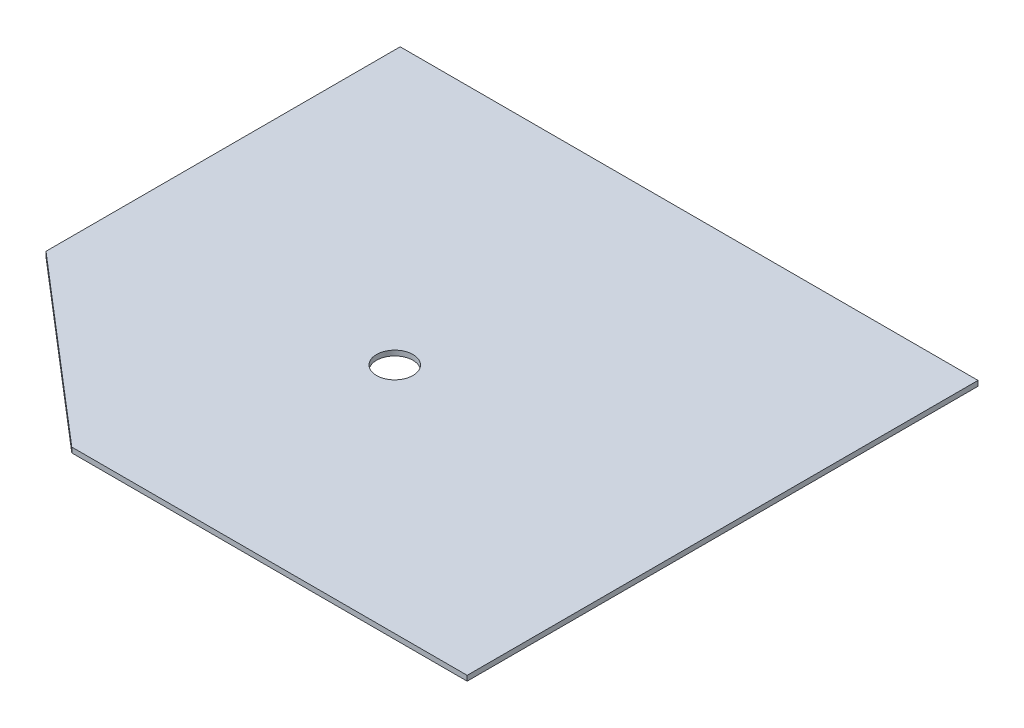
SolidWorks part; units mm, degrees
ref_plane "Front Plane" through (0, 0, 0) normal (0, 0, 1) x (1, 0, 0)
ref_plane "Top Plane" through (0, 0, 0) normal (0, 1, 0) x (1, 0, 0)
ref_plane "Right Plane" through (0, 0, 0) normal (1, 0, 0) x (0, 0, -1)
sketch "Sketch1" plane through (0, 0, 0) normal (0, 1, 0) x (1, 0, 0)
  line L1 (-213.645, -182.0895) -> (238.815, -182.0895)
  line L2 (-213.645, -182.0895) -> (-213.645, 217.9105)
  line L3 (-213.645, 217.9105) -> (238.815, 217.9105)
  line L4 (238.815, -182.0895) -> (238.815, 217.9105)
  dimension "D1" = 452.46
  dimension "D2" = 213.645
  dimension "D3" = 400
extrude "Boss-Extrude1" add sketch "Sketch1" along normal blind 4
sketch "Sketch2" plane through (0, 4, 0) normal (0, -1, 0) x (1, 0, 0)
  circle A0 centre (0, 0) radius 14.275
  dimension "D1" = 28.55
extrude "Cut-Extrude1" cut sketch "Sketch2" along normal through all
sketch "Sketch3" plane through (0, 4, 0) normal (0, 1, 0) x (1, 0, 0)
  line L0 (-70.7913, -182.0895) -> (-213.645, -59.422)
  line L1 (-213.645, -182.0895) -> (238.815, -182.0895) construction
  line L2 (-213.645, 217.9105) -> (-213.645, -182.0895) construction
  line L3 (-213.645, -59.422) -> (-317.3581, -168.1086)
  line L4 (-317.3581, -168.1086) -> (-142.2182, -320.0924)
  line L5 (-142.2182, -320.0924) -> (-70.7913, -182.0895)
extrude "Cut-Extrude2" cut sketch "Sketch3" against normal through all
